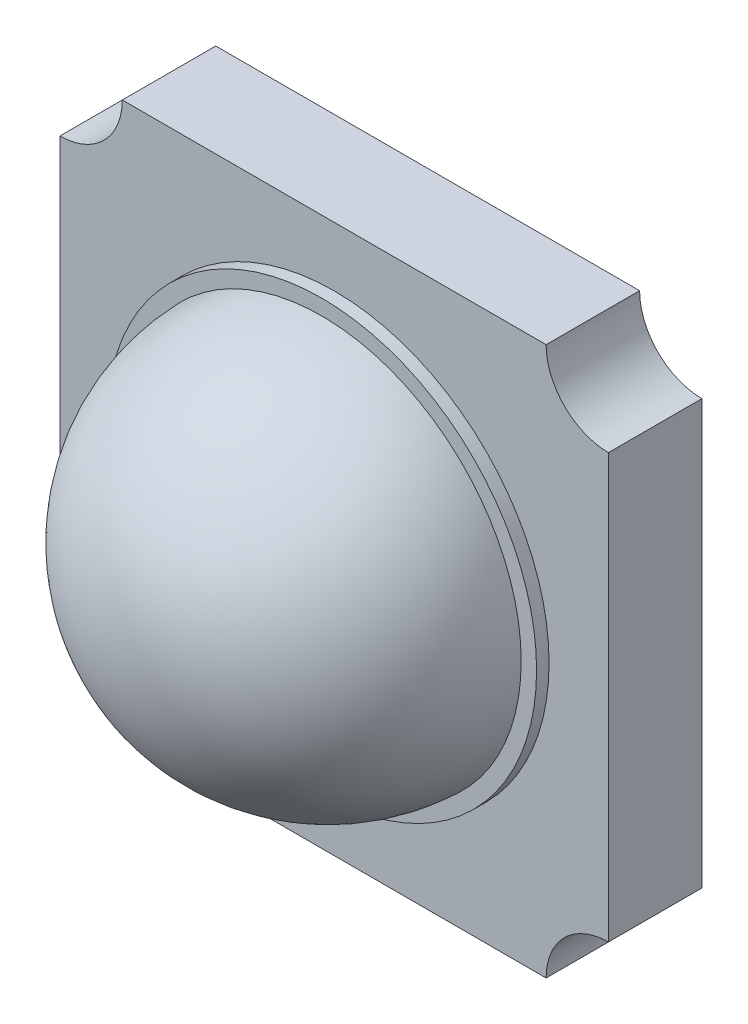
SolidWorks part; units mm, degrees
material "ABS"
ref_plane "Přední rovina" through (0, 0, 0) normal (0, 0, 1) x (1, 0, 0)
ref_plane "Horní rovina" through (0, 0, 0) normal (0, 1, 0) x (1, 0, 0)
ref_plane "Pravá rovina" through (0, 0, 0) normal (1, 0, 0) x (0, 0, -1)
sketch "Skica1" plane through (0, 0, 0) normal (0, 0, 1) x (1, 0, 0)
  line L0 (-51.6513, 37.0793) -> (-48.2513, 37.0793)
  line L1 (-52.1513, 36.5793) -> (-52.1513, 33.1793)
  line L2 (-51.6513, 32.6793) -> (-48.2513, 32.6793)
  line L3 (-47.7513, 33.1793) -> (-47.7513, 36.5793)
  arc A0 (-48.2513, 37.0793) -> (-47.7513, 36.5793) centre (-47.7513, 37.0793) ccw
  arc A4 (-51.6513, 37.0793) -> (-52.1513, 36.5793) centre (-52.1513, 37.0793) cw
  arc A5 (-47.7513, 33.1793) -> (-48.2513, 32.6793) centre (-47.7513, 32.6793) ccw
  arc A7 (-51.6513, 32.6793) -> (-52.1513, 33.1793) centre (-52.1513, 32.6793) ccw
  point P0 (-27.31, 16.6217)
  dimension "D1" = 4.4
  dimension "D2" = 4.4
extrude "Přidat vysunutím1" add sketch "Skica1" along normal blind 0.75
sketch "Skica2" plane through (0, 0, 0.75) normal (0, 0, 1) x (1, 0, 0)
  circle A0 centre (-49.9513, 34.8793) radius 1.6
sketch "Skica4" plane through (0, 0, 0.75) normal (0, 0, 1) x (1, 0, 0)
  circle A0 centre (-49.9513, 34.8793) radius 1.7237
extrude "Přidat vysunutím3" add sketch "Skica4" along normal blind 0.1
sketch "Skica5" plane through (0, 0, 0.75) normal (0, 0, 1) x (1, 0, 0)
  line L0 (-51.6513, 32.6793) -> (-48.2513, 37.0793)
  circle A0 centre (-49.9513, 34.8793) radius 1.6
extrude "Přidat vysunutím4" add sketch "Skica5" along normal blind 1.65 contours A0
fillet "Zaoblit7" radius 1.6 1 edges at (-48.3513, 34.8793, 2.4)
ref_plane "Rovina1" through (0, 0, 0) normal (0, 0, -1) x (-1, 0, 0)
sketch "Skica6" plane through (0, 0, 0) normal (0, 0, -1) x (-1, 0, 0)
  line L0 (49.9513, 37.0793) -> (49.9513, 32.6793) construction
  line L1 (48.2513, 37.0793) -> (51.6513, 37.0793) construction
  line L2 (51.6513, 32.6793) -> (48.2513, 32.6793) construction
  line L3 (52.1513, 34.8793) -> (47.7513, 34.8793) construction
  line L4 (52.1513, 36.5793) -> (52.1513, 33.1793) construction
  line L5 (47.7513, 33.1793) -> (47.7513, 36.5793) construction
  point P12 (49.9513, 34.8793)
